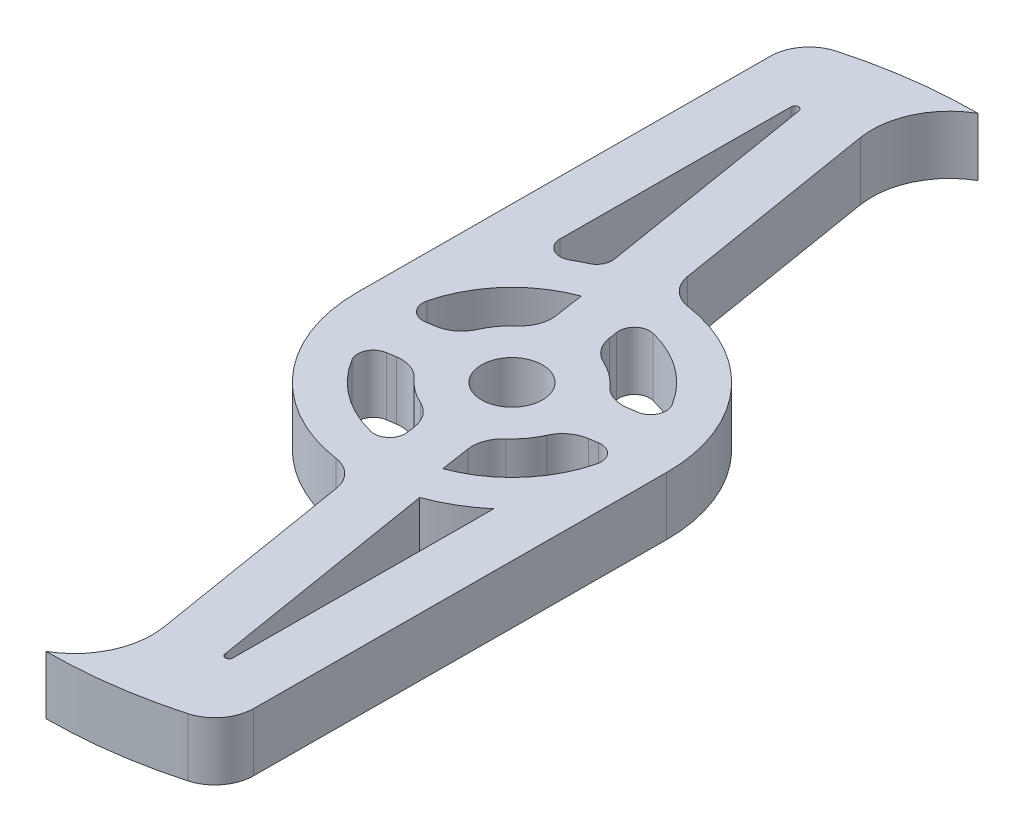
SolidWorks part; units mm, degrees
material "AISI Type A2 Tool Steel"
ref_plane "Front Plane" through (0, 0, 0) normal (0, 0, 1) x (1, 0, 0)
ref_plane "Top Plane" through (0, 0, 0) normal (0, 1, 0) x (1, 0, 0)
ref_plane "Right Plane" through (0, 0, 0) normal (1, 0, 0) x (0, 0, -1)
other "Bounding Box"
ref_plane "Default Plane" through (-8.9266, -12.7485, 0) normal (-0.1736, 0.9848, 0) x (0.9848, 0.1736, 0)
sketch "Sketch1" plane through (0, 0, 0) normal (0, 1, 0) x (1, 0, 0)
  circle A0 centre (0, 0) radius 12.7
  circle A1 centre (0, 0) radius 38.1 construction
  dimension "D1" = 76.2
  dimension "D2" = 25.4
extrude "Boss-Extrude1" add sketch "Sketch1" along normal mid plane 4.7625
sketch "Sketch2" plane through (0, 2.3813, 0) normal (0, 1, 0) x (1, 0, 0)
  line L0 (0, 0) -> (0, 38.1) construction
  line L1 (-3.0915, 31.5743) -> (0, 12.7)
  line L2 (0, 38.1) -> (-32.9956, 19.05) construction
  line L3 (-12.5224, 35.9833) -> (-12.6998, 0.0627)
  line L4 (-12.5224, 35.9833) -> (0, 38.1) construction
  circle A0 centre (0, 0) radius 38.1 construction
  arc A1 (-3.0915, 31.5743) -> (0, 38.1) centre (3.175, 32.6007) cw
  arc A2 (0, 38.1) -> (-12.5224, 35.9833) centre (0, 0) ccw
  circle A3 centre (0, 0) radius 12.7 construction
  arc A7 (-12.6998, 0.0627) -> (0, 12.7) centre (0, 0) cw
  point P7 (0, 13.1394)
  circle M2 centre (0, 0) radius 12.7
  dimension "D1" = 6.35
  dimension "D3" = 12.7
  dimension "D2" = 60
extrude "Boss-Extrude2" add sketch "Sketch2" against normal up to surface (4.7625 mm away) contours A1 A2 L3 L1 M2 region at (-7.3682, 2.3813, -22.8105) up to face at (0, -2.3813, 12.7)
pattern_circular "CirPattern1" count 2 over 360 about axis through (0, 2.3813, 0) along (0, -1, 0) of "Boss-Extrude2"
sketch "Sketch3" plane through (0, 2.3813, 0) normal (0, 1, 0) x (1, 0, 0)
  circle A0 centre (0, 0) radius 2.4892
  dimension "D1" = 4.9784
extrude "Cut-Extrude1" cut sketch "Sketch3" against normal through all
sketch "Sketch6" plane through (0, 2.3813, 0) normal (0, 1, 0) x (1, 0, 0)
  line L0 (-8.9412, -3.2833) -> (-4.9881, -2.6836)
  line L1 (-0.4836, -9.5127) -> (-1.0833, -5.5596)
  line L2 (-21.6442, -3.2838) -> (45641.2846, 6924.5369) construction
  line L3 (1.5982, -10.534) -> (-6926.2225, 45652.3948) construction
  line L4 (-8.9412, -3.2833) -> (-9.227, -1.3999) construction
  line L5 (-0.4836, -9.5127) -> (1.3999, -9.227) construction
  arc A0 (-1.0833, -5.5596) -> (-4.9881, -2.6836) centre (0, 0) cw
  arc A1 (-0.4836, -9.5127) -> (-8.9412, -3.2833) centre (0, 0) cw
  circle A2 centre (0, 0) radius 2.4892 construction
  circle A3 centre (0, 0) radius 12.7 construction
  point P15 (3.3081, -21.8042)
  dimension "D1" = 3.175
  dimension "D2" = 3.175
  dimension "D3" = 90
  dimension "D4" = 1.905
extrude "Cut-Extrude3" cut sketch "Sketch6" against normal through all
pattern_circular "CirPattern3" count 4 over 360 about axis through (0, -2.3813, 0) along (0, 1, 0) of "Cut-Extrude3"
sketch "Sketch5" plane through (0, 2.3813, 0) normal (0, 1, 0) x (1, 0, 0)
  line L6 (-8.0937, 32.6673) -> (-8.1023, 30.926) construction
  line L12 (-4.3865, 11.9815) -> (-7.478, 30.8558)
  line L13 (-8.0937, 32.6673) -> (-8.2549, 0.0408)
  line L14 (-4.3768, 11.922) -> (-7.478, 30.8558)
  line L15 (-8.1023, 30.926) -> (-8.2072, 9.6918)
  arc A4 (-8.1023, 30.926) -> (-7.4962, 30.9706) centre (-7.7975, 30.9245) cw
  arc A7 (-7.6185, 32.7814) -> (-7.478, 30.8558) centre (3.175, 32.6007) ccw
  arc A8 (-7.6185, 32.7814) -> (-8.0937, 32.6673) centre (0, 0) ccw
  arc A9 (-7.4962, 30.9706) -> (-7.478, 30.8558) centre (3.175, 32.6007) ccw
  arc A10 (-7.6185, 32.7814) -> (-8.0937, 32.6673) centre (0, 0) ccw construction
  arc A11 (-7.6185, 32.7814) -> (-7.4962, 30.9706) centre (3.175, 32.6007) ccw construction
  arc A12 (12.6998, -0.0627) -> (0, 12.7) centre (0, 0) ccw construction
  arc A13 (-4.3768, 11.922) -> (-8.2072, 9.6918) centre (0, 0) ccw
  point P0 (-7.8154, 31.2268)
  dimension "D2" = 0.3048
  dimension "D1" = 4.445
extrude "Cut-Extrude2" cut sketch "Sketch5" against normal through all both and the other way through all
pattern_circular "CirPattern2" count 2 over 360 about axis through (0, -2.3813, 0) along (0, 1, 0) of "Cut-Extrude2" reverse direction yes
fillet "Fillet3" radius 3.175 2 edges at (12.5224, 0, 35.9833) (-12.5224, 0, -35.9833)
fillet "Fillet4" radius 2.54 8 edges at (-5.5596, 0, -1.0833) (-2.6836, 0, -4.9881) (1.0833, 0, -5.5596) (4.9881, 0, -2.6836) (5.5596, 0, 1.0833) (2.6836, 0, 4.9881) (-4.9881, 0, 2.6836) (-1.0833, 0, 5.5596)
fillet "Fillet5" radius 1.27 8 edges at (8.9412, 0, -3.2833) (0.4836, 0, -9.5127) (-9.5127, 0, -0.4836) (-8.9412, 0, 3.2833) (-0.4836, 0, 9.5127) (9.5127, 0, 0.4836) (-8.2072, 0, -9.6918) (-4.3768, 0, -11.922)
fillet "Fillet6" radius 2.54 2 edges at (0, 0, 12.7) (0, 0, -12.7)
